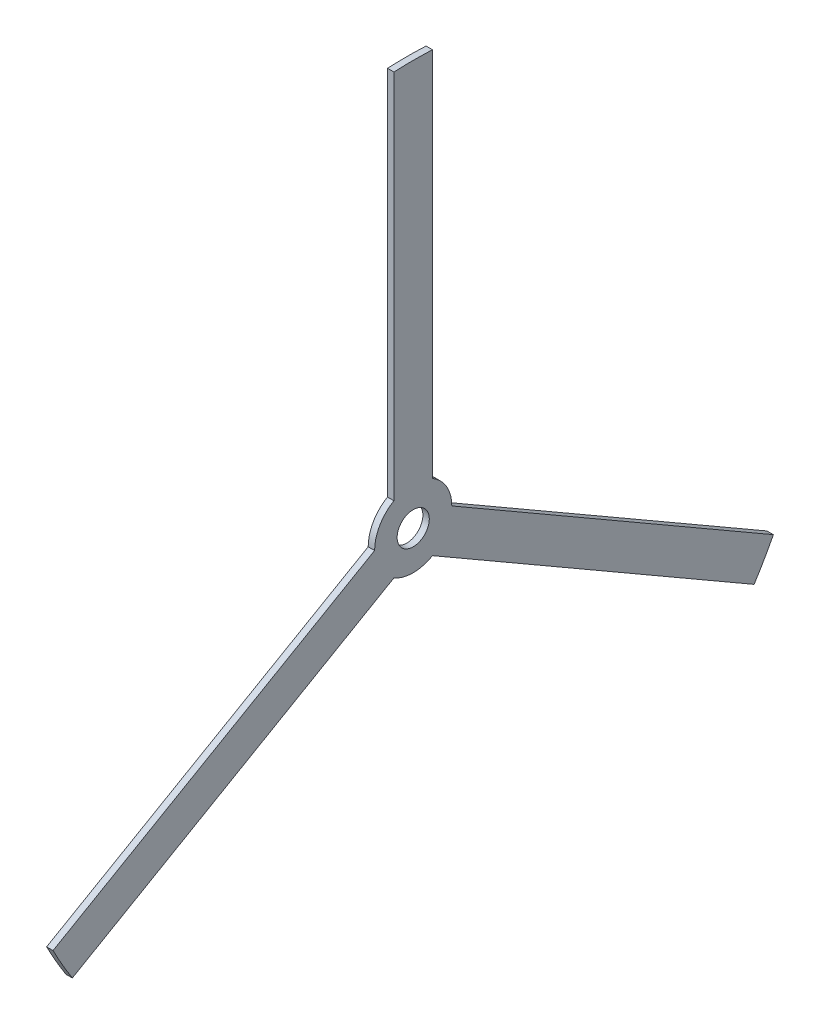
SolidWorks part; units mm, degrees
ref_plane "前视基准面" through (0, 0, 0) normal (0, 0, 1) x (1, 0, 0)
ref_plane "上视基准面" through (0, 0, 0) normal (0, 1, 0) x (1, 0, 0)
ref_plane "右视基准面" through (0, 0, 0) normal (1, 0, 0) x (0, 0, -1)
sketch "草图1" plane through (0, 0, 0) normal (1, 0, 0) x (0, 0, -1)
  circle A0 centre (0, 0) radius 63
  circle A1 centre (0, 0) radius 2.5
  dimension "D1" = 126
  dimension "D2" = 5
extrude "凸台-拉伸1" add sketch "草图1" along normal blind 1
sketch "草图2" plane through (0, 0, 0) normal (-1, 0, 0) x (0, 0, 1)
  line L9 (-3, 5.1962) -> (-3, 62.9285)
  line L17 (-6, 0) -> (-55.9977, -28.8662)
  arc A2 (-3, 62.9285) -> (-55.9977, -28.8662) centre (0, 0) ccw
  arc A6 (-3, 5.1962) -> (-6, 0) centre (0, 0) ccw
  point P3 (54.5596, -31.5)
  point P4 (0, 66.1907)
  point P8 (3, 0)
  point P9 (-71.9539, -41.5426)
  point P10 (3, 66.1907)
  point P11 (-3, 0)
  point P12 (-3, 66.1907)
  point P13 (1.5, 2.5981)
  point P14 (56.0596, -28.9019)
  point P15 (-1.5, -2.5981)
  point P16 (53.0596, -34.0981)
  point P17 (1.5, -2.5981)
  point P18 (-70.4539, -44.1407)
  point P19 (-1.5, 2.5981)
  point P20 (-73.4539, -38.9445)
extrude "切除-拉伸1" cut sketch "草图2" against normal blind 1
ref_axis "基准轴1" through (1.05, 0, 0) along (-1, 0, 0)
pattern_circular "阵列(圆周)1" count 3 over 360 about axis through (1.05, 0, 0) along (-1, 0, 0) of "切除-拉伸1"
